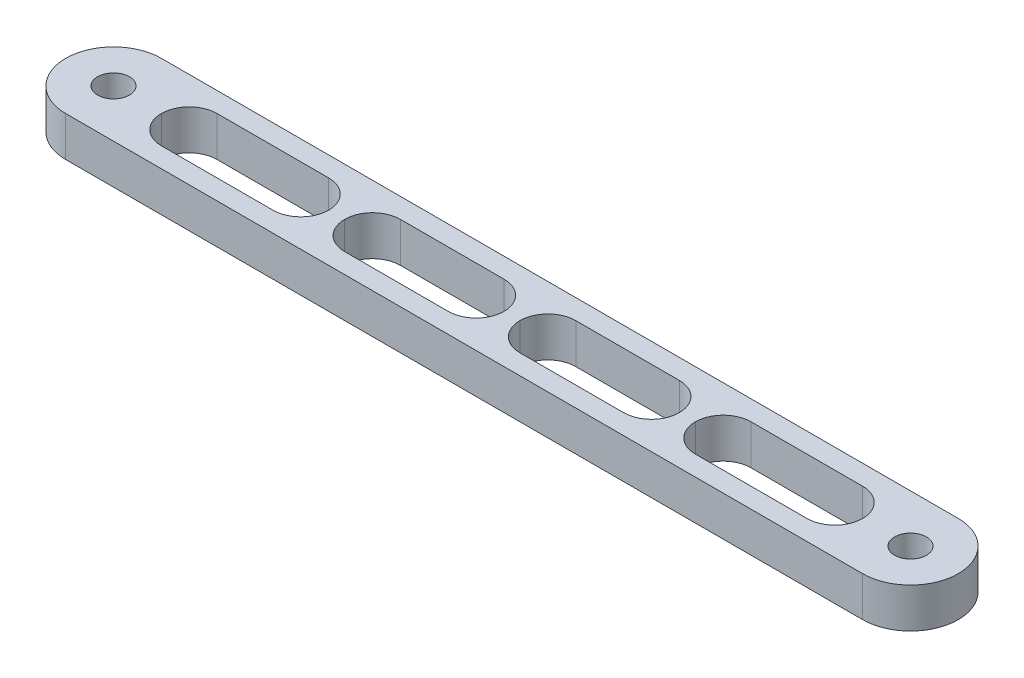
SolidWorks part; units mm, degrees
material "6063-T83"
ref_plane "Front Plane" through (0, 0, 0) normal (0, 0, 1) x (1, 0, 0)
ref_plane "Top Plane" through (0, 0, 0) normal (0, 1, 0) x (1, 0, 0)
ref_plane "Right Plane" through (0, 0, 0) normal (1, 0, 0) x (0, 0, -1)
sketch "Sketch1" plane through (0, 0, 0) normal (0, 1, 0) x (1, 0, 0)
  line L0 (-100, 7) -> (-100, -7) construction
  line L1 (-190.2532, -7) -> (-9.7468, -7) construction
  line L2 (-9.7468, 7) -> (-190.2532, 7) construction
  line L3 (-200, 12) -> (0, 12)
  line L5 (-56, 7) -> (-56, -7) construction
  line L6 (-188, 0) -> (-100, 0) construction
  line L7 (-100, 0) -> (-12, 0) construction
  line L8 (-144, 7) -> (-144, -7) construction
  line L9 (-188, 7) -> (-188, -7)
  line L10 (-146, 7) -> (-146, -7)
  line L11 (-142, 7) -> (-142, -7)
  line L12 (-102, 7) -> (-102, -7)
  line L13 (-98, 7) -> (-98, -7)
  line L14 (-58, 7) -> (-58, -7)
  line L15 (-54, 7) -> (-54, -7)
  line L16 (-12, 7) -> (-12, -7)
  line L17 (-146, 7) -> (-188, 7)
  line L18 (-188, -7) -> (-146, -7)
  line L19 (-142, -7) -> (-102, -7)
  line L20 (-102, 7) -> (-142, 7)
  line L21 (-98, 7) -> (-58, 7)
  line L22 (-98, -7) -> (-58, -7)
  line L23 (-54, -7) -> (-12, -7)
  line L24 (-54, 7) -> (-12, 7)
  line L25 (-200, 0) -> (-268.2656, 0) construction
  line L27 (-309.6741, -7) -> (-309.6741, 7) construction
  line L28 (-309.6741, 7) -> (-209.7468, 7) construction
  line L29 (-309.6741, -7) -> (-209.7468, -7) construction
  line L30 (-200, -12) -> (0, -12)
  circle A0 centre (0, 0) radius 12 construction
  circle A1 centre (-200, 0) radius 12 construction
  circle A2 centre (-200, 0) radius 4
  circle A3 centre (0, 0) radius 4
  arc A5 (0, -12) -> (0, 12) centre (0, 0) ccw
  arc A7 (-209.7468, 7) -> (-200, 12) centre (-200, 0) cw
  arc A8 (-200, -12) -> (-209.7468, -7) centre (-200, 0) cw
  circle A9 centre (-304.6741, 2) radius 2 construction
  arc A10 (-209.7468, 7) -> (-209.7468, -7) centre (-200, 0) ccw
  point P22 (-144, 0)
  point P28 (-56, 0)
  dimension "D2" = 24
  dimension "D3" = 24
  dimension "D4" = 8
  dimension "D5" = 8
  dimension "D18" = 4
  dimension "D1" = 200
  dimension "D6" = 5
  dimension "D7" = 5
  dimension "D8" = 7
  dimension "D9" = 7
  dimension "D10" = 2
  dimension "D11" = 2
  dimension "D12" = 2
  dimension "D13" = 2
  dimension "D14" = 2
  dimension "D15" = 2
  dimension "D16" = 5
  dimension "D17" = 5
extrude "Boss-Extrude1" add sketch "Sketch1" along normal blind 10
fillet "Fillet1" radius 7 16 edges at (-142, 5, -7) (-98, 5, -7) (-54, 5, -7) (-58, 5, -7) (-12, 5, -7) (-102, 5, -7) (-146, 5, -7) (-146, 5, 7) (-102, 5, 7) (-58, 5, 7) (-12, 5, 7) (-54, 5, 7) (-98, 5, 7) (-142, 5, 7) (-188, 5, 7) (-188, 5, -7)
